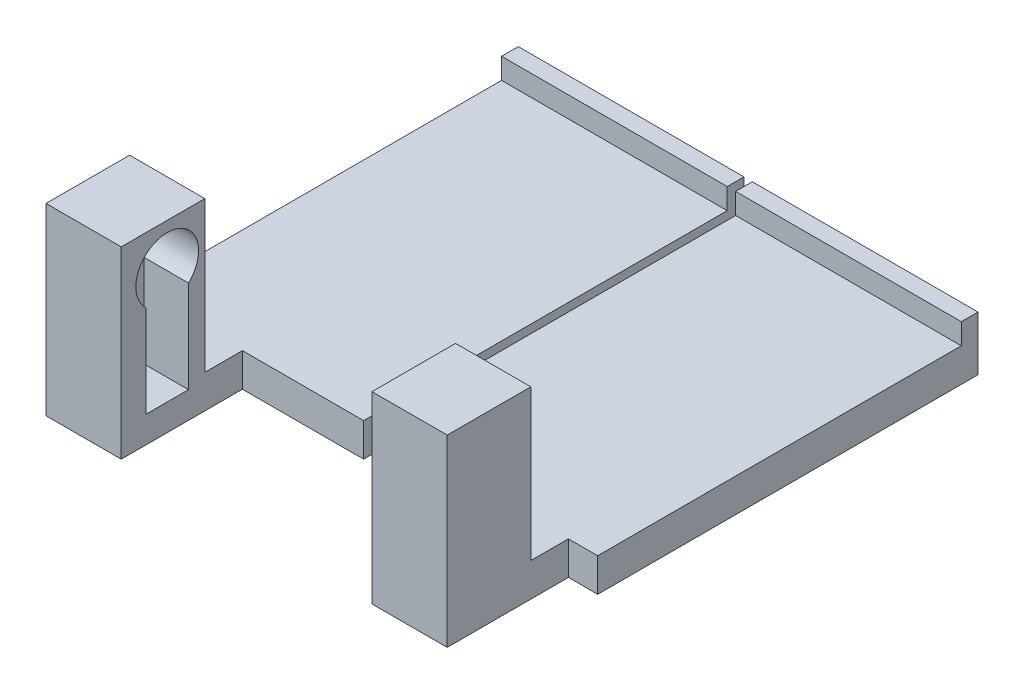
SolidWorks part; units mm, degrees
ref_plane "Front Plane" through (0, 0, 0) normal (0, 0, 1) x (1, 0, 0)
ref_plane "Top Plane" through (0, 0, 0) normal (0, 1, 0) x (1, 0, 0)
ref_plane "Right Plane" through (0, 0, 0) normal (1, 0, 0) x (0, 0, -1)
sketch "Sketch1" plane through (0, 0, 0) normal (1, 0, 0) x (0, 0, -1)
  line L1 (-3.5, -12.9783) -> (6.5, -12.9783)
  line L2 (-3.5, -12.9783) -> (-3.5, 5.0217)
  line L3 (-3.5, 5.0217) -> (6.5, 5.0217)
  line L4 (6.5, -12.9783) -> (6.5, 5.0217)
  line L5 (4.55, 0) -> (-0.55, 0)
  line L6 (4.55, 0) -> (4.55, -13.8)
  line L7 (-3.5, -12.9783) -> (56.5, -12.9783)
  line L8 (-3.5, -12.9783) -> (-3.5, -16.9783)
  line L9 (-3.5, -16.9783) -> (56.5, -16.9783)
  line L10 (56.5, -12.9783) -> (56.5, -16.9783)
  line L11 (-0.55, 0) -> (-0.55, -13.8)
  line L12 (4.55, -13.8) -> (-0.55, -13.8)
  line L13 (-3.5, 5.0217) -> (2, 5.0217)
  line L14 (2, 5.0217) -> (2, 0)
  line L15 (-3.5, -16.9783) -> (-3.5, -12.9783)
  line L16 (-3.5, -16.9783) -> (11, -16.9783)
  line L17 (-3.5, -12.9783) -> (11, -12.9783)
  line L18 (11, -16.9783) -> (11, -12.9783)
  circle A1 centre (2, 0) radius 3.75
  circle A2 centre (2, 0) radius 2.55
  point P0 (2, -13.8)
  dimension "D4" = 9
  dimension "D5" = 7.5
  dimension "D6" = 1.2
  dimension "D1" = 10
  dimension "D2" = 4
  dimension "D3" = 60
  dimension "D7" = 18
  dimension "D8" = 13.8
extrude "Boss-Extrude1" add sketch "Sketch1" along normal blind 9 contours L2 L1 L4 L3 | L15 L16 L18 L17
extrude "Cut-Extrude1" cut sketch "Sketch1<15>" along normal blind 5.3 contours A1 | L11 L12 L6 L5
sketch "Sketch1<15>" plane through (0, 0, 0) normal (1, 0, 0) x (0, 0, -1) same geometry as "Sketch1"
sketch "Sketch4" plane through (0, 0, -11) normal (0, 0, -1) x (-1, 0, 0)
extrude "Boss-Extrude2" add sketch "Sketch1<18>" along normal blind 12.5 and the other way blind 14.5 contours L18 L9 L10 L7 region at (0, -14.9783, -33.75)
sketch "Sketch1<18>" plane through (0, 0, 0) normal (1, 0, 0) x (0, 0, -1) same geometry as "Sketch1"
ref_plane "Plane8" through (0, -12.9783, 0) normal (0, 1, 0) x (1, 0, 0)
sketch "Sketch5" plane through (0, -12.9783, 0) normal (0, 1, 0) x (1, 0, 0)
  line L0 (12.5, 11) -> (12.5, 56.5) construction
  line L1 (-14.5, 56.5) -> (12.5, 56.5)
  line L2 (-14.5, 56.5) -> (-14.5, 54.5)
  line L3 (-14.5, 54.5) -> (12.5, 54.5)
  line L4 (12.5, 56.5) -> (12.5, 54.5)
extrude "Boss-Extrude3" add sketch "Sketch5" along normal blind 2.5
ref_plane "Plane9" through (-15, 0, 0) normal (1, 0, 0) x (0, 0, -1)
mirror "Mirror3" about plane through (-15, 0, 0) normal (1, 0, 0) of bodies 105
